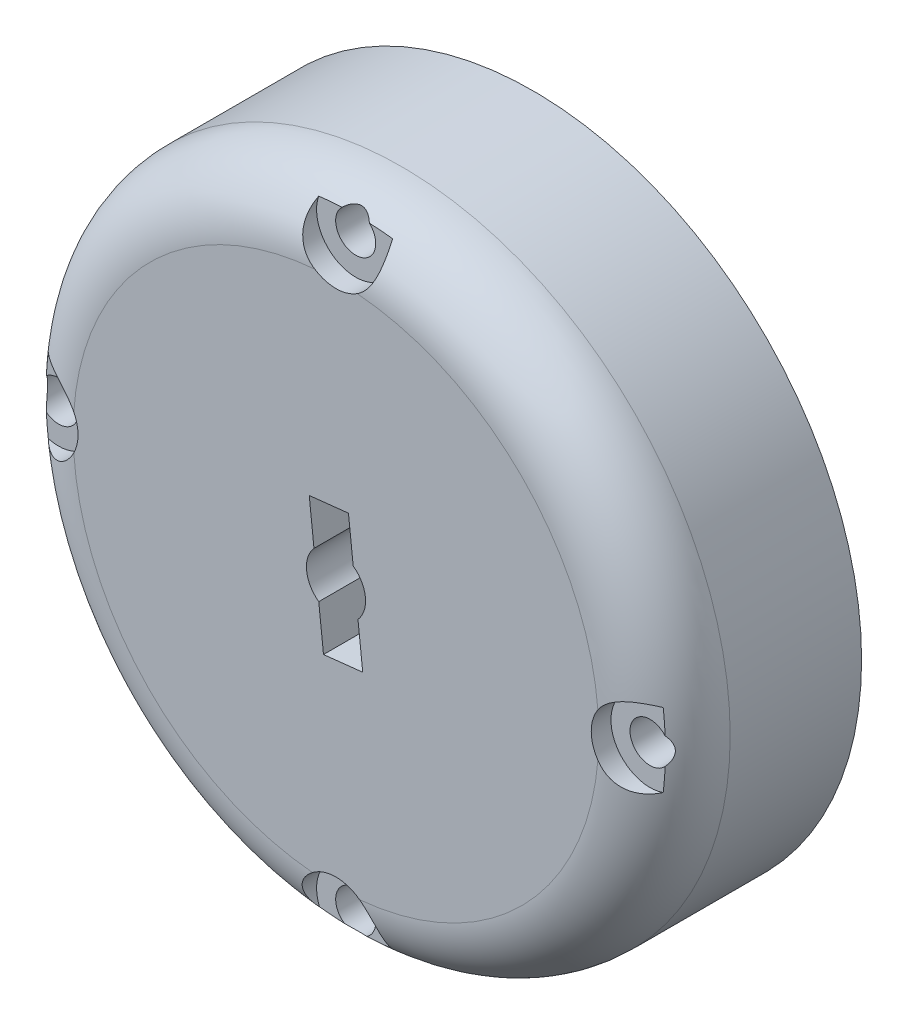
SolidWorks part; units mm, degrees
ref_plane "Front Plane" through (0, 0, 0) normal (0, 0, 1) x (1, 0, 0)
ref_plane "Top Plane" through (0, 0, 0) normal (0, 1, 0) x (1, 0, 0)
ref_plane "Right Plane" through (0, 0, 0) normal (1, 0, 0) x (0, 0, -1)
sketch "Sketch1" plane through (0, 0, 0) normal (0, 0, 1) x (1, 0, 0)
  circle A0 centre (0, 0) radius 19
  circle A1 centre (0, 0) radius 25
  dimension "D1" = 50
  dimension "D2" = 38
extrude "Boss-Extrude1" add sketch "Sketch1" along normal blind 5
sketch "Sketch2" plane through (0, 0, 5) normal (0, 0, 1) x (1, 0, 0)
  circle A0 centre (0, 0) radius 25 construction
  circle A1 centre (0, 0) radius 25
extrude "Boss-Extrude2" add sketch "Sketch2" along normal blind 10
fillet "Fillet1" radius 5 2 edges at (19, 0, 5) (25, 0, 15)
hole_wizard "CBORE for #3 Binding Head Machine Screw1" positions "Sketch13" profile "Sketch14" counterbore size "#3" standard "ANSI Inch" end condition through all
sketch "Sketch13" plane through (0, 0, 15) normal (0, 0, 1) x (1, 0, 0)
  point P0 (0, 22.4351)
  point P2 (0, -22.2959)
  point P4 (22.4003, 0)
  point P6 (-22.609, 0)
sketch "Sketch14" plane through (0, 22.4351, 15) normal (1, 0, 0) x (0, -1, 0)
  line L0 (0, 0) -> (0, 15)
  line L1 (0, 15) -> (1.524, 15)
  line L3 (1.524, 15) -> (1.524, 1.4986)
  line L4 (1.524, 1.4986) -> (2.9769, 1.4986)
  line L5 (2.9769, 1.4986) -> (2.9769, 0)
  line L7 (2.9769, 0) -> (0, 0)
  line L11 (0, -6.35) -> (0, 107.95) construction
  dimension "Thru Hole Dia." = 3.048
  dimension "Thru Hole Depth" = 15
  dimension "C'Bore Dia." = 5.9538
  dimension "C'Bore Depth" = 1.4986
sketch "Sketch15" plane through (0, 0, 5) normal (0, 0, -1) x (-1, 0, 0)
  line L6 (1.6762, 1.5009) -> (2.0371, 4.8073)
  line L7 (2.0371, 4.8073) -> (-0.9486, 5.1332)
  line L8 (-0.9486, 5.1332) -> (-1.3092, 1.8299)
  line L9 (-1.6731, -1.5044) -> (-2.0337, -4.8077)
  line L10 (-2.0337, -4.8077) -> (0.9521, -5.1336)
  line L11 (0.9521, -5.1336) -> (1.313, -1.8272)
  line L12 (1.6762, 1.5009) -> (2.0371, 4.8073)
  line L13 (2.0371, 4.8073) -> (-0.9486, 5.1332)
  line L14 (-0.9486, 5.1332) -> (-1.3092, 1.8299)
  line L15 (-1.6731, -1.5044) -> (-2.0337, -4.8077)
  line L16 (-2.0337, -4.8077) -> (0.9521, -5.1336)
  line L17 (0.9521, -5.1336) -> (1.313, -1.8272)
  arc A4 (2.2367, -0.2441) -> (1.6762, 1.5009) centre (0, 0) ccw
  arc A5 (-1.3092, 1.8299) -> (-2.2367, 0.2441) centre (0, 0) ccw
  arc A6 (-2.2367, 0.2441) -> (-1.6731, -1.5044) centre (0, 0) ccw
  arc A7 (1.313, -1.8272) -> (2.2367, -0.2441) centre (0, 0) ccw
  arc A8 (2.2367, -0.2441) -> (1.6762, 1.5009) centre (0, 0) ccw
  arc A9 (-1.3092, 1.8299) -> (-2.2367, 0.2441) centre (0, 0) ccw
  arc A10 (-2.2367, 0.2441) -> (-1.6731, -1.5044) centre (0, 0) ccw
  arc A11 (1.313, -1.8272) -> (2.2367, -0.2441) centre (0, 0) ccw
  dimension "D1" = 0
extrude "Cut-Extrude1" cut sketch "Sketch15" against normal blind 10 from offset 3 offset against normal yes
scale "Scale1" scale about centroid uniform scaling yes scale factor 1.5
